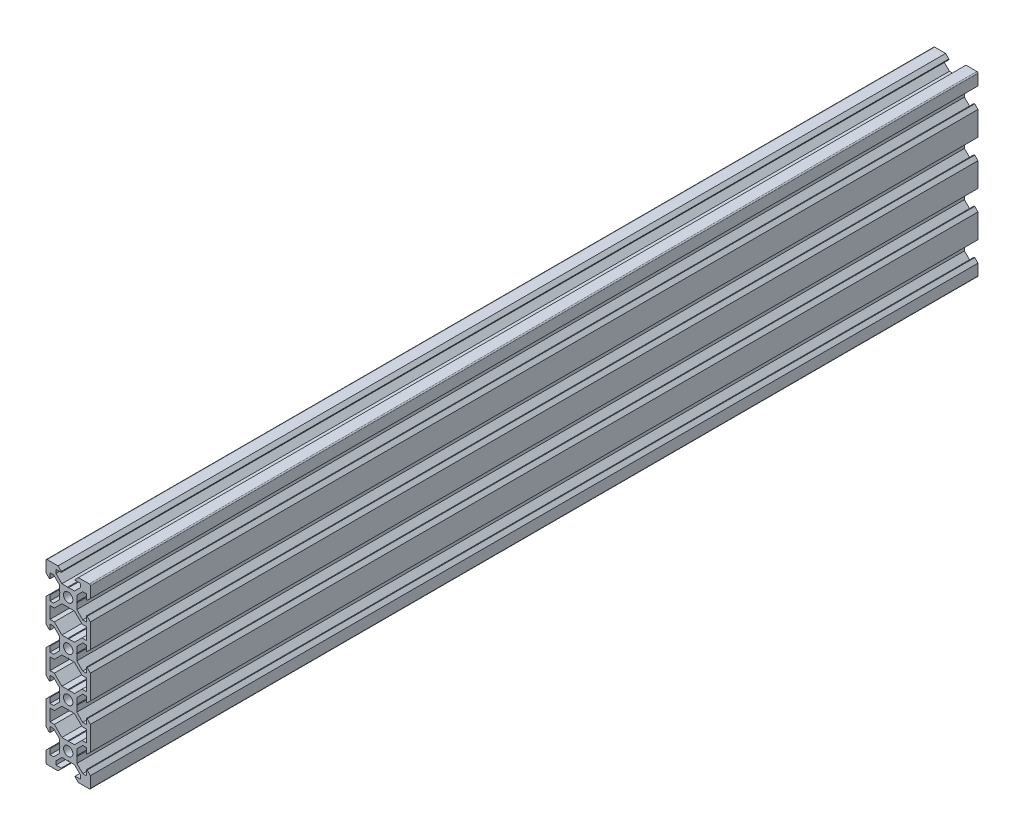
SolidWorks part; units mm, degrees
ref_plane "Plan de face" through (0, 0, 0) normal (0, 0, 1) x (1, 0, 0)
ref_plane "Plan de dessus" through (0, 0, 0) normal (0, 1, 0) x (1, 0, 0)
ref_plane "Plan de droite" through (0, 0, 0) normal (1, 0, 0) x (0, 0, -1)
ref_axis "Axe" through (0, 0, -13.782) along (0, 0, 1)
sketch "Esquisse1" plane through (0, 0, 0) normal (0, 0, 1) x (1, 0, 0)
  line L0 (0, 27.6392) -> (0, -27.6392) construction
  line L1 (-33.6074, 0) -> (33.6074, 0) construction
  line L2 (0, 0) -> (-22.2114, 22.2114) construction
  line L3 (-9.5, 10) -> (-4.58, 10)
  line L4 (-4.58, 10) -> (-3.125, 8.545)
  line L5 (-3.125, 8.545) -> (-3.125, 8.2)
  line L6 (-3.125, 8.2) -> (-5.5, 8.2)
  line L7 (-2.8393, 3.9) -> (-5.5, 6.5607)
  line L8 (-2.8393, 3.9) -> (-0.21, 3.9)
  line L9 (-5.5, 6.5607) -> (-5.5, 8.2)
  line L10 (0, 3.69) -> (0, 2.1)
  line L11 (-3.9, 2.8393) -> (-6.5607, 5.5)
  line L12 (-8.545, 3.125) -> (-8.2, 3.125)
  line L13 (-8.2, 3.125) -> (-8.2, 5.5)
  line L14 (-6.5607, 5.5) -> (-8.2, 5.5)
  line L15 (-10, 4.58) -> (-8.545, 3.125)
  line L16 (-10, 9.5) -> (-10, 4.58)
  line L17 (-0.21, 3.9) -> (0, 3.69)
  line L18 (-3.9, 2.8393) -> (-3.9, 0.21)
  line L19 (-6.2393, -12.7) -> (-8.2, -12.7)
  line L20 (-3.9, 0.21) -> (-3.69, 0)
  line L21 (-0.21, -3.9) -> (0, -3.69)
  line L22 (0, -3.69) -> (0, -2.1)
  line L23 (-6.5607, -5.5) -> (-8.2, -5.5)
  line L24 (-2.8393, -3.9) -> (-0.21, -3.9)
  line L25 (-8.545, -3.125) -> (-8.2, -3.125)
  line L26 (-10, -4.58) -> (-8.545, -3.125)
  line L27 (-8.2, -3.125) -> (-8.2, -5.5)
  line L28 (-2.8393, -3.9) -> (-6.2393, -7.3)
  line L29 (-3.9, -2.8393) -> (-6.5607, -5.5)
  line L30 (-3.9, -2.8393) -> (-3.9, -0.21)
  line L31 (-3.9, -0.21) -> (-3.69, 0)
  line L32 (-6.2393, -7.3) -> (-8.2, -7.3)
  line L33 (-8.2, -7.3) -> (-8.2, -12.7)
  line L34 (-8.2, -10) -> (-10, -10) construction
  line L35 (-10, -15.42) -> (-10, -4.58)
  line L36 (-3.9, -19.79) -> (-3.69, -20)
  line L37 (-3.9, -17.1607) -> (-3.9, -19.79)
  line L38 (-3.9, -17.1607) -> (-6.5607, -14.5)
  line L39 (-2.8393, -16.1) -> (-6.2393, -12.7)
  line L40 (-8.2, -16.875) -> (-8.2, -14.5)
  line L41 (-10, -15.42) -> (-8.545, -16.875)
  line L42 (-8.545, -16.875) -> (-8.2, -16.875)
  line L43 (-2.8393, -16.1) -> (-0.21, -16.1)
  line L44 (-6.5607, -14.5) -> (-8.2, -14.5)
  line L45 (0, -16.31) -> (0, -17.9)
  line L46 (-0.21, -16.1) -> (0, -16.31)
  line L47 (-8.2, -30) -> (-10, -30) construction
  line L48 (-3.69, -20) -> (0, -20) construction
  line L49 (-0.21, -23.9) -> (0, -23.69)
  line L50 (0, -23.69) -> (0, -22.1)
  line L51 (-6.5607, -25.5) -> (-8.2, -25.5)
  line L52 (-2.8393, -23.9) -> (-0.21, -23.9)
  line L53 (-8.545, -23.125) -> (-8.2, -23.125)
  line L54 (-10, -24.58) -> (-8.545, -23.125)
  line L55 (-8.2, -23.125) -> (-8.2, -25.5)
  line L56 (-2.8393, -23.9) -> (-6.2393, -27.3)
  line L57 (-3.9, -22.8393) -> (-6.5607, -25.5)
  line L58 (-3.9, -22.8393) -> (-3.9, -20.21)
  line L59 (-3.9, -20.21) -> (-3.69, -20)
  line L60 (-10, -24.58) -> (-10, -35.42)
  line L61 (-8.2, -32.7) -> (-8.2, -27.3)
  line L62 (-3.69, -40) -> (0, -40) construction
  line L63 (-8.2, -50) -> (-10, -50) construction
  line L64 (0, -60) -> (-22.2114, -82.2114) construction
  line L65 (-33.6074, -60) -> (33.6074, -60) construction
  line L66 (0, -87.6392) -> (0, -32.3608) construction
  line L67 (-6.2393, -32.7) -> (-8.2, -32.7)
  line L68 (-3.9, -39.79) -> (-3.69, -40)
  line L69 (-3.9, -37.1607) -> (-3.9, -39.79)
  line L70 (-3.9, -37.1607) -> (-6.5607, -34.5)
  line L71 (-2.8393, -36.1) -> (-6.2393, -32.7)
  line L72 (-8.2, -36.875) -> (-8.2, -34.5)
  line L73 (-10, -35.42) -> (-8.545, -36.875)
  line L74 (-8.545, -36.875) -> (-8.2, -36.875)
  line L75 (-6.2393, -27.3) -> (-8.2, -27.3)
  line L76 (-2.8393, -36.1) -> (-0.21, -36.1)
  line L77 (-6.5607, -34.5) -> (-8.2, -34.5)
  line L78 (0, -36.31) -> (0, -37.9)
  line L79 (-0.21, -36.1) -> (0, -36.31)
  line L80 (-0.21, -43.9) -> (0, -43.69)
  line L81 (0, -43.69) -> (0, -42.1)
  line L82 (-6.5607, -45.5) -> (-8.2, -45.5)
  line L83 (-2.8393, -43.9) -> (-0.21, -43.9)
  line L84 (-8.545, -43.125) -> (-8.2, -43.125)
  line L85 (-10, -44.58) -> (-8.545, -43.125)
  line L86 (-8.2, -43.125) -> (-8.2, -45.5)
  line L87 (-2.8393, -43.9) -> (-6.2393, -47.3)
  line L88 (-3.9, -42.8393) -> (-6.5607, -45.5)
  line L89 (-3.9, -42.8393) -> (-3.9, -40.21)
  line L90 (-3.9, -40.21) -> (-3.69, -40)
  line L91 (-10, -44.58) -> (-10, -55.42)
  line L92 (-8.2, -52.7) -> (-8.2, -47.3)
  line L93 (-6.2393, -52.7) -> (-8.2, -52.7)
  line L94 (-3.9, -59.79) -> (-3.69, -60)
  line L95 (-3.9, -57.1607) -> (-3.9, -59.79)
  line L96 (-3.9, -57.1607) -> (-6.5607, -54.5)
  line L97 (-2.8393, -56.1) -> (-6.2393, -52.7)
  line L98 (-8.2, -56.875) -> (-8.2, -54.5)
  line L99 (-10, -55.42) -> (-8.545, -56.875)
  line L100 (-8.545, -56.875) -> (-8.2, -56.875)
  line L101 (-2.8393, -56.1) -> (-0.21, -56.1)
  line L102 (-6.5607, -54.5) -> (-8.2, -54.5)
  line L103 (0, -56.31) -> (0, -57.9)
  line L104 (-0.21, -56.1) -> (0, -56.31)
  line L105 (-3.9, -60.21) -> (-3.69, -60)
  line L106 (-6.2393, -47.3) -> (-8.2, -47.3)
  line L107 (-3.9, -62.8393) -> (-3.9, -60.21)
  line L108 (-0.21, -63.9) -> (0, -63.69)
  line L109 (-10, -69.5) -> (-10, -64.58)
  line L110 (-10, -64.58) -> (-8.545, -63.125)
  line L111 (-6.5607, -65.5) -> (-8.2, -65.5)
  line L112 (-8.2, -63.125) -> (-8.2, -65.5)
  line L113 (-8.545, -63.125) -> (-8.2, -63.125)
  line L114 (-3.9, -62.8393) -> (-6.5607, -65.5)
  line L115 (0, -63.69) -> (0, -62.1)
  line L116 (-5.5, -66.5607) -> (-5.5, -68.2)
  line L117 (-2.8393, -63.9) -> (-0.21, -63.9)
  line L118 (-2.8393, -63.9) -> (-5.5, -66.5607)
  line L119 (-3.125, -68.2) -> (-5.5, -68.2)
  line L120 (-3.125, -68.545) -> (-3.125, -68.2)
  line L121 (-4.58, -70) -> (-3.125, -68.545)
  line L122 (-9.5, -70) -> (-4.58, -70)
  arc A0 (0, -2.1) -> (0, 2.1) centre (0, 0) cw
  arc A1 (-9.5, 10) -> (-10, 9.5) centre (-9.5, 9.5) ccw
  arc A2 (0, -42.1) -> (0, -37.9) centre (0, -40) cw
  arc A3 (-9.5, -70) -> (-10, -69.5) centre (-9.5, -69.5) cw
  arc A4 (0, -17.9) -> (0, -22.1) centre (0, -20) ccw
  arc A5 (0, -57.9) -> (0, -62.1) centre (0, -60) ccw
  point P4 (0, 0)
  point P7 (0, 0)
  point P30 (-10, 10)
  point P60 (0, -20)
  point P146 (-10, -70)
  dimension "D5" = 11
  dimension "D2" = 2.1
  dimension "D3" = 6.25
  dimension "D10" = 0.5
  dimension "D4" = 9.16
  dimension "D6" = 1.5
  dimension "D7" = 1.8
  dimension "D8" = 4.3
  dimension "D9" = 20
  dimension "D11" = 0.42
  dimension "D12" = 10
  dimension "D13" = 1.8
extrude "Boss.-Extru.1" add sketch "Esquisse1" along normal blind 400
sketch "Esquisse3" plane through (0, 0, 400) normal (0, 0, 1) x (1, 0, 0)
  line L0 (0, 0) -> (-9.8536, 9.8536) construction
  line L1 (-8.2, 8.2) -> (-8.2, 6.57)
  line L2 (-8.2, 6.57) -> (-7.54, 6.57)
  line L3 (-7.54, 6.57) -> (-6.57, 7.54)
  line L4 (-8.2, 3.125) -> (-8.2, 5.5) construction
  line L5 (-6.57, 8.2) -> (-6.57, 7.54)
  line L6 (-8.2, 8.2) -> (-6.57, 8.2)
  line L7 (-5.5, 6.5607) -> (-5.5, 8.2) construction
  line L8 (-10, -30) -> (6.918, -30) construction
  line L9 (-10, -24.58) -> (-10, -35.42) construction
  line L10 (-8.2, -68.2) -> (-6.57, -68.2)
  line L11 (-6.57, -68.2) -> (-6.57, -67.54)
  line L12 (-7.54, -66.57) -> (-6.57, -67.54)
  line L13 (-8.2, -66.57) -> (-7.54, -66.57)
  line L14 (-8.2, -68.2) -> (-8.2, -66.57)
  arc A0 (-9.5, 10) -> (-10, 9.5) centre (-9.5, 9.5) ccw construction
  point P13 (-7.055, 7.055)
  point P14 (-6.57, 7.87)
  point P26 (-7.055, -67.055)
  dimension "D1" = 1.07
extrude "Enlèv. mat.-Extru.1" [suppressed] cut sketch "Esquisse3" against normal through all
mirror "Symétrie1" about plane through (0, 3.69, 400) normal (-1, 0, 0) of "Enlèv. mat.-Extru.1", "Boss.-Extru.1"
